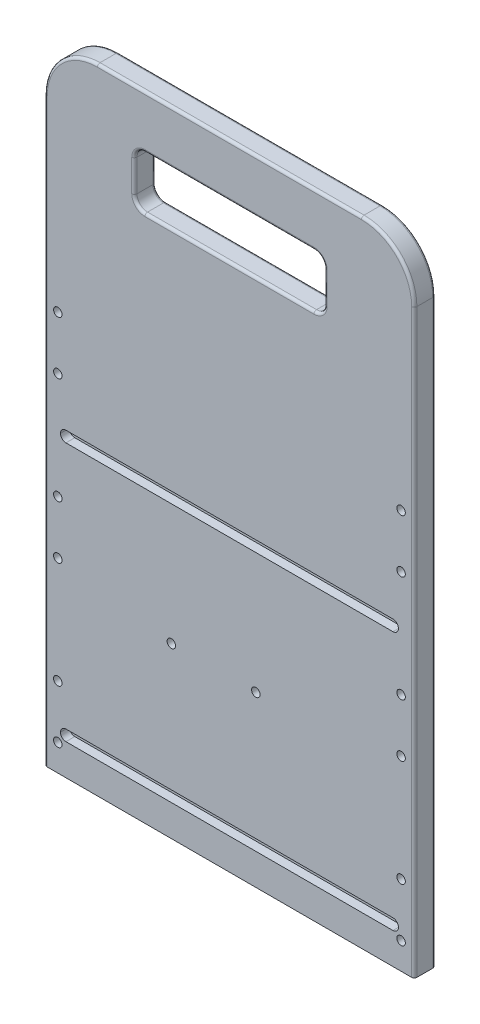
SolidWorks part; units mm, degrees
material "PE High Density"
ref_plane "Front Plane" through (0, 0, 0) normal (0, 0, 1) x (1, 0, 0)
ref_plane "Top Plane" through (0, 0, 0) normal (0, 1, 0) x (1, 0, 0)
ref_plane "Right Plane" through (0, 0, 0) normal (1, 0, 0) x (0, 0, -1)
sketch "Sketch1" plane through (0, 0, 0) normal (0, 0, 1) x (1, 0, 0)
  line L1 (-111.125, -190.5) -> (111.125, -190.5)
  line L2 (-111.125, -190.5) -> (-111.125, 190.5)
  line L3 (-111.125, 190.5) -> (111.125, 190.5)
  line L4 (111.125, -190.5) -> (111.125, 190.5)
  line L5 (-111.125, -190.5) -> (111.125, 190.5) construction
  line L6 (-111.125, 190.5) -> (111.125, -190.5) construction
  point P0 (0, 0)
  dimension "D1" = 222.25
  dimension "D2" = 381
extrude "Boss-Extrude1" add sketch "Sketch1" along normal blind 12.7 contours L3 L4 L1 L2
fillet "Fillet1" radius 31.75 2 edges at (-111.125, 190.5, 6.35) (111.125, 190.5, 6.35)
sketch "Sketch2" plane through (0, 0, 12.7) normal (0, 0, 1) x (1, 0, 0)
  line L0 (-79.375, 190.5) -> (79.375, 190.5) construction
  line L1 (-57.15, 158.75) -> (57.15, 158.75)
  line L2 (-57.15, 158.75) -> (-57.15, 127)
  line L3 (-57.15, 127) -> (57.15, 127)
  line L4 (57.15, 158.75) -> (57.15, 127)
  point P4 (0, 127)
  dimension "D1" = 114.3
  dimension "D2" = 31.75
  dimension "D3" = 31.75
extrude "Cut-Extrude1" cut sketch "Sketch2" against normal up to surface (12.7 mm away) up to face at (0, 55.1085, 0)
fillet "Fillet2" radius 6.35 4 edges at (57.15, 127, 6.35) (57.15, 158.75, 6.35) (-57.15, 158.75, 6.35) (-57.15, 127, 6.35)
sketch "Sketch3" plane through (0, 0, 12.7) normal (0, 0, 1) x (1, 0, 0)
  line L0 (-111.125, -190.5) -> (111.125, -190.5) construction
  line L1 (-101.6, -171.704) -> (101.6, -171.704)
  line L2 (-101.6, -171.704) -> (-101.6, -165.1)
  line L3 (-101.6, -165.1) -> (101.6, -165.1)
  line L4 (101.6, -171.704) -> (101.6, -165.1)
  line L6 (-101.6, -16.129) -> (101.6, -16.129)
  line L7 (-101.6, -16.129) -> (-101.6, -9.525)
  line L8 (-101.6, -9.525) -> (101.6, -9.525)
  line L9 (101.6, -16.129) -> (101.6, -9.525)
  point P4 (0, -165.1)
  point P12 (0, -16.129)
  dimension "D1" = 18.796
  dimension "D2" = 6.604
  dimension "D3" = 203.2
  dimension "D4" = 203.2
  dimension "D5" = 6.604
  dimension "D6" = 174.371
extrude "Cut-Extrude2" cut sketch "Sketch3" against normal blind 5.334
fillet "Fillet3" radius 3.302 8 edges at (101.6, -165.1, 10.033) (101.6, -171.704, 10.033) (-101.6, -171.704, 10.033) (-101.6, -165.1, 10.033) (101.6, -16.129, 10.033) (101.6, -9.525, 10.033) (-101.6, -9.525, 10.033) (-101.6, -16.129, 10.033)
hole_wizard "CSK for #10 Flat Head Machine Screw1" positions "Sketch6" profile "Sketch8" countersink size "#10" standard "ANSI Inch"
sketch "Sketch6" plane through (0, 0, 0) normal (0, 0, -1) x (-1, 0, 0)
  line L0 (111.125, -190.5) -> (-111.125, -190.5) construction
  line L1 (-111.125, -190.5) -> (-111.125, 158.75) construction
  line L2 (111.125, -190.5) -> (111.125, 158.75) construction
  line L3 (111.125, -190.5) -> (111.125, 158.75) construction
  line L4 (103.1875, -174.5) -> (103.1875, -142.5) construction
  point P0 (-103.1875, -174.5)
  point P6 (103.1875, -174.5)
  point P43 (-15.875, -88.9)
  point P45 (34.925, -88.9)
  point P66 (-103.1875, -142.5)
  point P67 (103.1875, -142.5)
  point P68 (-103.1875, -110.5)
  point P69 (103.1875, -110.5)
  point P70 (-103.1875, -78.5)
  point P71 (103.1875, -78.5)
  point P72 (-103.1875, -46.5)
  point P73 (103.1875, -46.5)
  point P74 (-103.1875, -14.5)
  point P75 (103.1875, -14.5)
  point P76 (-103.1875, 17.5)
  point P77 (103.1875, 17.5)
  point P78 (-103.1875, 49.5)
  point P79 (103.1875, 49.5)
  dimension "D1" = 16
  dimension "D2" = 7.9375
  dimension "D3" = 7.9375
  dimension "D8" = 50.8
  dimension "D10" = 101.6
  dimension "D9" = 76.2
  dimension "D5" = 32
sketch "Sketch8" plane through (103.1875, -174.5, 0) normal (1, 0, 0) x (0, 1, 0)
  line L0 (0, 0) -> (0, 12.7)
  line L1 (0, 12.7) -> (2.5527, 12.7)
  line L2 (2.5527, 12.7) -> (2.5527, 2.6882)
  line L3 (2.5527, 2.6882) -> (4.8895, 0)
  line L5 (4.8895, 0) -> (0, 0)
  line L6 (-2.5527, 2.6882) -> (-4.8895, 0) construction
  line L11 (0, -6.35) -> (0, 107.95) construction
  dimension "Thru Hole Dia." = 5.1054
  dimension "Thru Hole Depth" = 12.7
  dimension "Near C'Sink Dia." = 9.779
  dimension "Near C'Sink Angle" = 82
fillet "Fillet4" radius 1.5875 26 edges at (-55.2901, 128.8599, 12.7) (-57.15, 142.875, 12.7) (-55.2901, 156.8901, 12.7) (0, 158.75, 12.7) (55.2901, 156.8901, 12.7) (57.15, 142.875, 12.7) (55.2901, 128.8599, 12.7) (-55.2901, 128.8599, 0) (-57.15, 142.875, 0) (-55.2901, 156.8901, 0) (0, 158.75, 0) (55.2901, 156.8901, 0) (57.15, 142.875, 0) (55.2901, 128.8599, 0) (-111.125, -15.875, 0) (-101.8256, 181.2006, 0) (111.125, -15.875, 0) (101.8256, 181.2006, 0) (111.125, -15.875, 12.7) (101.8256, 181.2006, 12.7) (0, 190.5, 12.7) (-101.8256, 181.2006, 12.7) (0, 127, 12.7) (0, 127, 0) (0, 190.5, 0) (-111.125, -15.875, 12.7)
equation "\"D4@Sketch3\"=\"D3@Sketch3\""
equation "\"D5@Sketch3\"=\"D2@Sketch3\""
equation "\"D3@Sketch6\"=\"D2@Sketch6\""
equation "\"D6@Sketch3\"=7.240in-.375"
equation "\"D1@Sketch6\"=16mm"
equation "\"D5@Sketch6\"=32mm"
